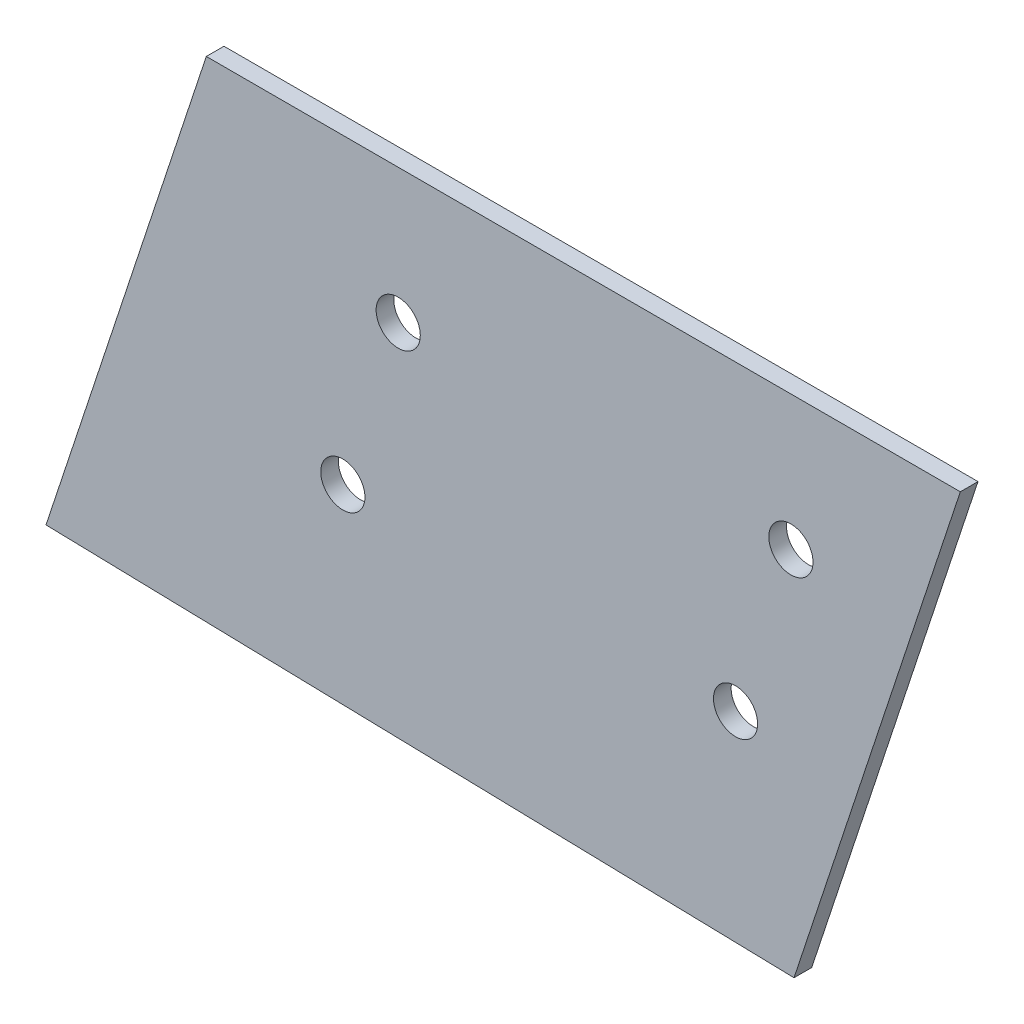
SolidWorks part; units mm, degrees
ref_plane "Front Plane" through (0, 0, 0) normal (0, 0, 1) x (1, 0, 0)
ref_plane "Top Plane" through (0, 0, 0) normal (0, 1, 0) x (1, 0, 0)
ref_plane "Right Plane" through (0, 0, 0) normal (1, 0, 0) x (0, 0, -1)
sketch "Sketch2" plane through (0, 0, 0) normal (0, 0, 1) x (1, 0, 0)
  line L0 (-54.6192, -24.5892) -> (30.7248, -24.5892)
  line L1 (-54.6192, -24.5892) -> (-71.4913, -75.7257)
  line L2 (30.7248, -24.5892) -> (13.8527, -75.7257)
  line L3 (-71.4913, -75.7257) -> (13.8527, -75.7257)
  dimension "D1" = 85.344
  dimension "D2" = 53.848
  dimension "D3" = 108.26
extrude "Boss-Extrude1" add sketch "Sketch2" along normal blind 2
sketch "Sketch3" plane through (0, 0, 2) normal (0, 0, 1) x (1, 0, 0)
  line L0 (-72.7647, -79.585) -> (11.9014, -81.6395)
  line L2 (-71.4913, -75.7257) -> (-72.7647, -79.585)
  line L3 (-72.7647, -79.585) -> (18.6346, -79.585) construction
  line L4 (-54.6192, -24.5892) -> (-71.4913, -75.7257) construction
  line L5 (13.8527, -75.7257) -> (11.9014, -81.6395)
  line L6 (13.8527, -75.7257) -> (30.7248, -24.5892) construction
  line L7 (-71.4913, -75.7257) -> (13.8527, -75.7257)
  dimension "D1" = 1.39
  dimension "D2" = 180
  dimension "D3" = 180
  dimension "D4" = 4.064
extrude "Boss-Extrude2" add sketch "Sketch3" against normal blind 2
sketch "Sketch4" plane through (0, 0, 2) normal (0, 0, 1) x (1, 0, 0)
  line L0 (-32.9007, -39.8292) -> (-39.1673, -58.8221) construction
  line L1 (-39.1673, -58.8221) -> (5.2827, -58.8221) construction
  line L2 (5.2827, -58.8221) -> (11.5493, -39.8292) construction
  line L3 (11.5493, -39.8292) -> (-32.9007, -39.8292) construction
  line L4 (-54.6192, -24.5892) -> (-72.7647, -79.585) construction
  line L5 (30.7248, -24.5892) -> (-54.6192, -24.5892) construction
  circle A0 centre (-32.9007, -39.8292) radius 2.5
  circle A1 centre (11.5493, -39.8292) radius 2.5
  circle A2 centre (5.2827, -58.8221) radius 2.5
  circle A3 centre (-39.1673, -58.8221) radius 2.5
  dimension "D1" = 5
  dimension "D2" = 44.45
  dimension "D3" = 20
  dimension "D4" = 25.4
  dimension "D5" = 15.24
extrude "Cut-Extrude2" cut sketch "Sketch4" against normal up to surface (2 mm away) up to face at (-21.1894, -52.6007, 0)
